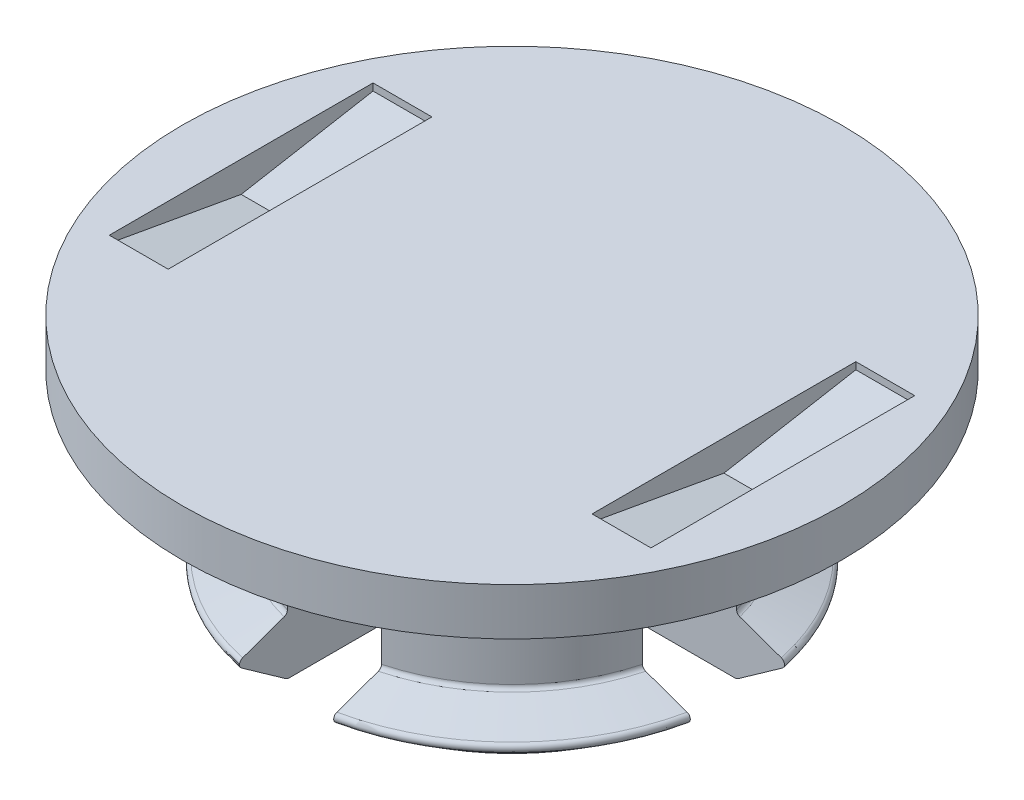
SolidWorks part; units mm, degrees
ref_plane "Front Plane" through (0, 0, 0) normal (0, 0, 1) x (1, 0, 0)
ref_plane "Top Plane" through (0, 0, 0) normal (0, 1, 0) x (1, 0, 0)
ref_plane "Right Plane" through (0, 0, 0) normal (1, 0, 0) x (0, 0, -1)
sketch "Szkic1" plane through (0, 0, 0) normal (0, 1, 0) x (1, 0, 0)
  circle A0 centre (0, 0) radius 7
  dimension "D1" = 14
extrude "Dodanie-wyciągnięcie1" add sketch "Szkic1" along normal blind 1
ref_point "Punkt1"
ref_plane "Płaszczyzna1" through (0, 0, 0) normal (0, -1, 0) x (-1, 0, 0)
sketch "Szkic2" plane through (0, 0, 0) normal (0, -1, 0) x (-1, 0, 0)
  circle A0 centre (0, 0) radius 3.9
  dimension "D1" = 7.8
extrude "Dodanie-wyciągnięcie2" add sketch "Szkic2" along normal blind 4.3
ref_axis "Oś1" through (0, -4.3, 0) along (0, 1, 0)
sketch "Szkic3" plane through (0, 0, 0) normal (1, 0, 0) x (0, 0, -1)
  line L1 (3.9, -4.3) -> (5, -3.5004)
  line L2 (5, -3.5004) -> (3.9, -3.1)
  line L4 (3.9, -3.1) -> (3.9, -4.3)
  line L5 (0, -4.3) -> (0, 0) construction
  line L7 (-7.7, 0) -> (7.7, 0) construction
  dimension "D1" = 3.9
  dimension "D2" = 1.2
  dimension "D3" = 70
  dimension "D4" = 4.3
  dimension "D5" = 5
revolve "Obrót1" add sketch "Szkic3" angle 360 about axis through (0, -4.3, 0) along (0, 1, 0)
fillet "Zaokrąglenie1" radius 0.1 3 edges at (0, -3.5004, -5) (0, -3.1, -3.9) (0, -4.3, -3.9)
ref_plane "Płaszczyzna2" through (0, -4.3, 0) normal (0, -1, 0) x (-1, 0, 0)
sketch "Szkic5" plane through (0, -4.3, 0) normal (0, -1, 0) x (-1, 0, 0)
  line L0 (-7.7941, -1) -> (-1, -1)
  line L1 (7.7941, 1) -> (1, 1)
  line L2 (-1, -7.7941) -> (-1, -1)
  line L3 (1, 7.7941) -> (1, 1)
  line L4 (-1, 1) -> (-1, 7.7941)
  line L5 (1, -1) -> (7.7941, -1)
  line L6 (1, -1) -> (1, -7.7941)
  line L7 (-1, 1) -> (-7.7941, 1)
  line L8 (-1, -1) -> (1, 1) construction
  arc A0 (-7.7941, 1) -> (-7.7941, -1) centre (0, 0) ccw
  arc A1 (-1, -7.7941) -> (1, -7.7941) centre (0, 0) ccw
  arc A2 (7.7941, -1) -> (7.7941, 1) centre (0, 0) ccw
  arc A3 (1, 7.7941) -> (-1, 7.7941) centre (0, 0) ccw
  point P1 (0, 0)
  dimension "D1" = 2
  dimension "D2" = 2
extrude "Wytnij-wyciągnięcie1" cut sketch "Szkic5" against normal blind 4.3
ref_plane "płaszczyzna dolna" through (0, 1, 0) normal (0, 1, 0) x (1, 0, 0)
sketch "Szkic8" plane through (0, 1, 0) normal (0, 1, 0) x (1, 0, 0)
  line L0 (4.5, -2.8) -> (-4.5, 2.8) construction
  line L1 (5.75, -2.8) -> (4.5, -2.8)
  line L2 (5.75, -2.8) -> (5.75, 2.8)
  line L3 (5.75, 2.8) -> (4.5, 2.8)
  line L4 (4.5, -2.8) -> (4.5, 2.8)
  line L5 (-4.5, -2.8) -> (-5.75, -2.8)
  line L6 (-4.5, -2.8) -> (-4.5, 2.8)
  line L7 (-4.5, 2.8) -> (-5.75, 2.8)
  line L8 (-5.75, -2.8) -> (-5.75, 2.8)
  point P8 (0, 0)
  dimension "D1" = 5.6
  dimension "D2" = 1.25
  dimension "D3" = 9
extrude "Wytnij-wyciągnięcie2" cut sketch "Szkic8" against normal blind 0.65
sketch "Szkic10" plane through (5.75, 0, 0) normal (-1, 0, 0) x (0, 0, 1)
  line L0 (-2.8, 0.85) -> (-2.8, 0.35)
  line L1 (-2.8, 0.35) -> (-2.8, 1) construction
  line L2 (-2.8, 0.35) -> (0, 0.35)
  line L3 (2.8, 0.35) -> (-2.8, 0.35) construction
  line L4 (0, 0.35) -> (2.8, 0.35)
  line L5 (2.8, 0.35) -> (2.8, 0.85)
  line L7 (2.8, 0.85) -> (0, 0.35)
  line L8 (-2.8, 0.85) -> (0, 0.35)
  line L9 (2.8, 0.35) -> (2.8, 1) construction
  line M6 (-2.8, 1) -> (-2.8, 0.35)
  line M7 (-2.8, 0.35) -> (2.8, 0.35)
  line M8 (2.8, 0.35) -> (2.8, 1)
  dimension "D1" = 0.5
extrude "Dodanie-wyciągnięcie3" add sketch "Szkic10" along normal blind 12 contours L8 M6 M7 | L7 M8 M7 region at (5.75, 0.5167, -1.8667) region at (5.75, 0.5167, 1.8667)
